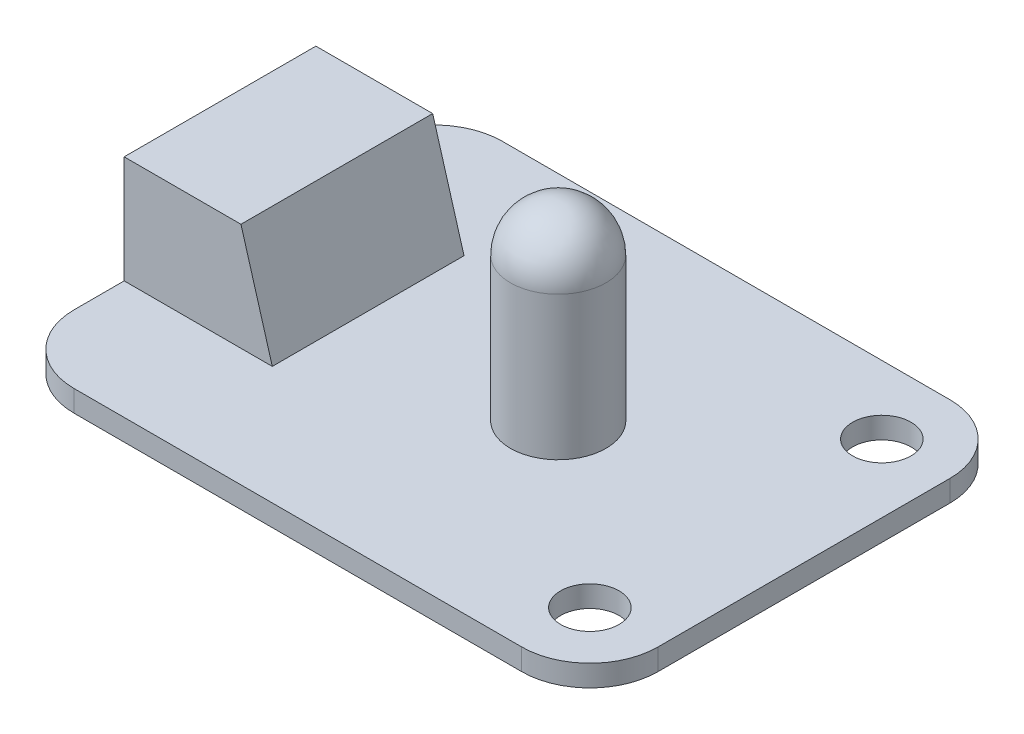
SolidWorks part; units mm, degrees
ref_plane "Front Plane" through (0, 0, 0) normal (0, 0, 1) x (1, 0, 0)
ref_plane "Top Plane" through (0, 0, 0) normal (0, 1, 0) x (1, 0, 0)
ref_plane "Right Plane" through (0, 0, 0) normal (1, 0, 0) x (0, 0, -1)
sketch "Sketch1" plane through (0, 0, 0) normal (0, 1, 0) x (1, 0, 0)
  line L4 (3.5, 0) -> (26.5, 0)
  line L5 (30, 3.5) -> (30, 18.5)
  line L6 (26.5, 22) -> (3.5, 22)
  line L7 (0, 18.5) -> (0, 3.5)
  arc A0 (26.5, 0) -> (30, 3.5) centre (26.5, 3.5) ccw
  arc A1 (3.5, 0) -> (0, 3.5) centre (3.5, 3.5) cw
  arc A2 (3.5, 22) -> (0, 18.5) centre (3.5, 18.5) ccw
  arc A3 (30, 18.5) -> (26.5, 22) centre (26.5, 18.5) ccw
  circle A4 centre (26.5, 18.5) radius 1.5
  circle A5 centre (26.5, 3.5) radius 1.5
  point P7 (0, 0)
  point P10 (0, 0)
  dimension "D1" = 22
  dimension "D5" = 3.5
  dimension "D3" = 3.5
  dimension "D4" = 3.5
  dimension "D6" = 3.5
  dimension "D7" = 3
  dimension "D8" = 3
  dimension "D2" = 30
extrude "Boss-Extrude1" add sketch "Sketch1" along normal blind 1.1
sketch "Sketch2" plane through (0, 1.1, 0) normal (0, 1, 0) x (1, 0, 0)
  line L0 (26.5, 22) -> (3.5, 22) construction
  line L1 (30, 3.5) -> (30, 18.5) construction
  circle A0 centre (17.375, 11) radius 2.455
  dimension "D1" = 4.91
  dimension "D2" = 11
  dimension "D3" = 12.625
extrude "Boss-Extrude2" add sketch "Sketch2" along normal blind 7.365
dome "Dome1" faces to dome 1 distance 2.455 reverse direction no elliptical dome no face at (17.375, 8.465, -8.545) parameters "D1"=2.455
sketch "Sketch9" plane through (0, 1.1, 0) normal (0, 1, 0) x (1, 0, 0)
  line L0 (0, 15.925) -> (6, 15.925)
  line L1 (0, 18.5) -> (0, 3.5) construction
  line L2 (6, 15.925) -> (6, 6.075)
  line L3 (6, 6.075) -> (0, 6.075)
  line L4 (0, 6.075) -> (0, 15.925)
  line L5 (26.5, 22) -> (3.5, 22) construction
  point P4 (0, 11)
  dimension "D1" = 9.85
  dimension "D2" = 6
  dimension "D3" = 11
extrude "Boss-Extrude3" add sketch "Sketch9" along normal blind 5.52
sketch "Sketch10" plane through (0, 0, -6.075) normal (0, 0, 1) x (1, 0, 0)
  line L0 (0, 1.1) -> (7.61, 1.1)
  line L1 (3.5, 1.1) -> (26.5, 1.1) construction
  line L2 (7.61, 1.1) -> (6, 6.62)
sketch "Sketch11" plane through (0, 0, -15.925) normal (0, 0, -1) x (-1, 0, 0)
  line L0 (0, 1.1) -> (-7.61, 1.1)
  line L1 (-7.61, 1.1) -> (-6, 6.62)
  line L2 (-6, 6.62) -> (0, 6.62)
  line L3 (0, 6.62) -> (0, 1.1)
extrude "Boss-Extrude4" add sketch "Sketch11" against normal blind 9.85
